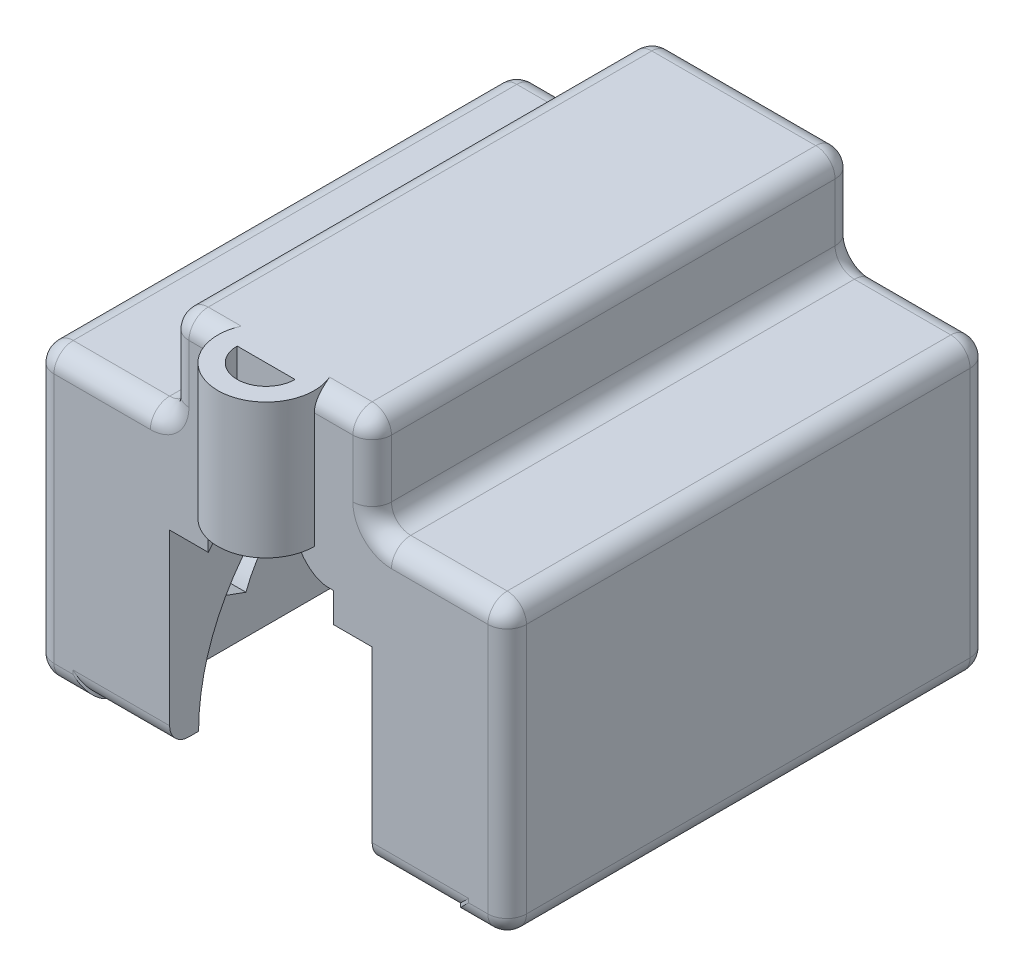
SolidWorks part; units mm, degrees
ref_plane "Front Plane" through (0, 0, 0) normal (0, 0, 1) x (1, 0, 0)
ref_plane "Top Plane" through (0, 0, 0) normal (0, 1, 0) x (1, 0, 0)
ref_plane "Right Plane" through (0, 0, 0) normal (1, 0, 0) x (0, 0, -1)
sketch "Sketch2" plane through (0, 0, 0) normal (0, 0, 1) x (1, 0, 0)
  line L0 (0, 0) -> (0, 38.1)
  line L1 (0, 38.1) -> (17.78, 38.1)
  line L2 (17.78, 38.1) -> (17.78, 50.8)
  line L3 (17.78, 50.8) -> (44.45, 50.8)
  line L4 (44.45, 50.8) -> (44.45, 38.1)
  line L5 (44.45, 38.1) -> (62.23, 38.1)
  line L6 (62.23, 38.1) -> (62.23, 0)
  line L8 (54.61, 0) -> (62.23, 0)
  line L9 (54.61, 0) -> (54.61, 0.508)
  line L10 (54.61, 0.508) -> (7.62, 0.508)
  line L11 (7.62, 0.508) -> (7.62, 0)
  line L12 (7.62, 0) -> (0, 0)
  dimension "D1" = 38.1
  dimension "D2" = 12.7
  dimension "D3" = 12.7
  dimension "D4" = 17.78
  dimension "D5" = 17.78
  dimension "D6" = 7.62
  dimension "D7" = 7.62
  dimension "D8" = 46.99
  dimension "D9" = 0.508
  dimension "D10" = 38.1
extrude "Boss-Extrude1" add sketch "Sketch2" along normal blind 58.42
sketch "Sketch3" plane through (0, 0.508, 0) normal (0, -1, 0) x (1, 0, 0)
  line L0 (7.62, 58.42) -> (54.61, 58.42) construction
  line L1 (7.62, 0) -> (54.61, 0) construction
  line L2 (7.62, 58.42) -> (7.62, 0) construction
  line L3 (54.61, 58.42) -> (54.61, 0) construction
  line L12 (10.16, 3.81) -> (52.07, 3.81)
  line L13 (52.07, 3.81) -> (52.07, 54.61)
  line L14 (52.07, 54.61) -> (10.16, 54.61)
  line L15 (10.16, 54.61) -> (10.16, 3.81)
  dimension "D1" = 3.81
  dimension "D2" = 3.81
  dimension "D3" = 2.54
  dimension "D4" = 2.54
extrude "Cut-Extrude1" cut sketch "Sketch3" against normal blind 2.54
sketch "Sketch15" plane through (0, 0.508, 0) normal (0, -1, 0) x (-1, 0, 0)
  line L0 (-52.07, -29.21) -> (-10.16, -29.21) construction
  line L1 (-52.07, -3.81) -> (-52.07, -54.61) construction
  line L2 (-10.16, -54.61) -> (-10.16, -3.81) construction
  line L3 (-52.07, -29.21) -> (-52.07, -54.61)
  line L4 (-52.07, -54.61) -> (-10.16, -54.61)
  line L6 (-10.16, -54.61) -> (-10.16, -29.21)
  line L7 (-10.16, -3.81) -> (-52.07, -3.81) construction
  line L8 (-52.07, -54.61) -> (-10.16, -54.61) construction
  line L9 (-52.07, -29.21) -> (-10.16, -29.21)
  dimension "D1" = 0
revolve "Cut-Revolve2" cut sketch "Sketch15" angle 360 about L0
sketch "Sketch17" plane through (0, 0.508, 0) normal (0, -1, 0) x (1, 0, 0)
  line L0 (52.07, 3.81) -> (52.07, 54.61) construction
  line L1 (46.99, 1.27) -> (15.24, 1.27)
  line L2 (46.99, 1.27) -> (46.99, 29.21)
  line L3 (46.99, 29.21) -> (15.24, 29.21)
  line L4 (15.24, 1.27) -> (15.24, 29.21)
  line L5 (7.62, 58.42) -> (7.62, 0) construction
  line L6 (54.61, 58.42) -> (54.61, 0) construction
  line L7 (7.62, 0) -> (54.61, 0) construction
  point P12 (52.07, 29.21)
  dimension "D1" = 0
  dimension "D2" = 7.62
  dimension "D3" = 7.62
  dimension "D4" = 1.27
revolve "Cut-Revolve3" cut sketch "Sketch17" angle 230 about L3 other way angle 20
sketch "Sketch18" plane through (0, 0.508, 0) normal (0, -1, 0) x (1, 0, 0)
  line L0 (10.16, 3.81) -> (15.24, 3.81) construction
  line L1 (52.07, 29.21) -> (46.99, 29.21)
  line L2 (52.07, 29.21) -> (52.07, 47.752)
  line L3 (52.07, 47.752) -> (46.99, 47.752)
  line L4 (46.99, 29.21) -> (46.99, 47.752)
  line L5 (10.16, 47.752) -> (15.24, 47.752)
  line L6 (10.16, 47.752) -> (10.16, 29.21)
  line L7 (10.16, 29.21) -> (15.24, 29.21)
  line L8 (15.24, 47.752) -> (15.24, 29.21)
  line L33 (52.07, 3.81) -> (52.07, 54.61) construction
  line L34 (10.16, 29.21) -> (52.07, 29.21) construction
  line L35 (10.16, 54.61) -> (52.07, 54.61) construction
  line L36 (15.24, 57.15) -> (15.24, 54.61) construction
  line L38 (46.99, 54.61) -> (46.99, 57.15) construction
  line L41 (10.16, 47.752) -> (7.62, 47.752)
  line L42 (10.16, 47.752) -> (10.16, 44.196)
  line L43 (10.16, 44.196) -> (7.62, 44.196)
  line L44 (7.62, 47.752) -> (7.62, 44.196)
  line L45 (10.16, 54.61) -> (15.24, 54.61) construction
  line L46 (52.07, 47.752) -> (54.61, 47.752)
  line L47 (52.07, 47.752) -> (52.07, 44.196)
  line L48 (52.07, 44.196) -> (54.61, 44.196)
  line L49 (54.61, 47.752) -> (54.61, 44.196)
  line L51 (10.16, 54.61) -> (10.16, 3.81) construction
  point P34 (12.7, 3.81)
  dimension "D1" = 25.4
  dimension "D2" = 6.858
  dimension "D3" = 3.556
  dimension "D4" = 6.858
  dimension "D5" = 2.54
  dimension "D6" = 0
  dimension "D7" = 3.556
  dimension "D8" = 2.54
sketch "Sketch19" plane through (0, 0, 0) normal (0, 0, -1) x (-1, 0, 0)
  line L24 (-7.62, 0) -> (0, 0)
  line L25 (0, 0) -> (0, 38.1)
  line L26 (0, 38.1) -> (-17.78, 38.1)
  line L27 (-17.78, 38.1) -> (-17.78, 50.8)
  line L28 (-17.78, 50.8) -> (-44.45, 50.8)
  line L29 (-44.45, 50.8) -> (-44.45, 38.1)
  line L30 (-44.45, 38.1) -> (-62.23, 38.1)
  line L31 (-62.23, 38.1) -> (-62.23, 0)
  line L32 (-62.23, 0) -> (-54.61, 0)
  line L33 (-54.61, 0) -> (-54.61, 0.508)
  line L34 (-54.61, 0.508) -> (-7.62, 0.508)
  line L35 (-7.62, 0.508) -> (-7.62, 0)
  line L36 (-7.62, 0) -> (0, 0)
  line L37 (0, 0) -> (0, 38.1)
  line L38 (0, 38.1) -> (-17.78, 38.1)
  line L39 (-17.78, 38.1) -> (-17.78, 50.8)
  line L40 (-17.78, 50.8) -> (-44.45, 50.8)
  line L41 (-44.45, 50.8) -> (-44.45, 38.1)
  line L42 (-44.45, 38.1) -> (-62.23, 38.1)
  line L43 (-62.23, 38.1) -> (-62.23, 0)
  line L44 (-62.23, 0) -> (-54.61, 0)
  line L45 (-54.61, 0) -> (-54.61, 0.508)
  line L46 (-54.61, 0.508) -> (-7.62, 0.508)
  line L47 (-7.62, 0.508) -> (-7.62, 0)
  dimension "D1" = 0
extrude "Boss-Extrude2" add sketch "Sketch19" along normal blind 2.54
sketch "Sketch20" plane through (0, 0, 58.42) normal (0, 0, 1) x (1, 0, 0)
  line L24 (0, 0) -> (7.62, 0)
  line L25 (7.62, 0) -> (7.62, 0.508)
  line L26 (7.62, 0.508) -> (54.61, 0.508)
  line L27 (54.61, 0.508) -> (54.61, 0)
  line L28 (54.61, 0) -> (62.23, 0)
  line L29 (62.23, 0) -> (62.23, 38.1)
  line L30 (62.23, 38.1) -> (44.45, 38.1)
  line L31 (44.45, 38.1) -> (44.45, 50.8)
  line L32 (44.45, 50.8) -> (17.78, 50.8)
  line L33 (17.78, 50.8) -> (17.78, 38.1)
  line L34 (17.78, 38.1) -> (0, 38.1)
  line L35 (0, 38.1) -> (0, 0)
  line L36 (0, 0) -> (7.62, 0)
  line L37 (7.62, 0) -> (7.62, 0.508)
  line L38 (7.62, 0.508) -> (54.61, 0.508)
  line L39 (54.61, 0.508) -> (54.61, 0)
  line L40 (54.61, 0) -> (62.23, 0)
  line L41 (62.23, 0) -> (62.23, 38.1)
  line L42 (62.23, 38.1) -> (44.45, 38.1)
  line L43 (44.45, 38.1) -> (44.45, 50.8)
  line L44 (44.45, 50.8) -> (17.78, 50.8)
  line L45 (17.78, 50.8) -> (17.78, 38.1)
  line L46 (17.78, 38.1) -> (0, 38.1)
  line L47 (0, 38.1) -> (0, 0)
  dimension "D1" = 0
extrude "Boss-Extrude3" add sketch "Sketch20" along normal blind 2.54
revolve "Cut-Revolve4" cut sketch "Sketch18" angle 340 about L34 region at (49.53, 0.508, 38.481) region at (12.7, 0.508, 38.481) region at (8.89, 0.508, 45.974)
fillet "Fillet2" radius 2.54 32 edges at (62.23, 0, 29.21) (62.23, 38.1, 29.21) (44.45, 38.1, 29.21) (0, 0, 29.21) (0, 38.1, 29.21) (17.78, 38.1, 29.21) (44.45, 50.8, 29.21) (17.78, 50.8, 29.21) (53.34, 38.1, 60.96) (53.34, 38.1, -2.54) (62.23, 19.05, 60.96) (62.23, 19.05, -2.54) (44.45, 44.45, 60.96) (44.45, 44.45, -2.54) (0, 19.05, 60.96) (0, 19.05, -2.54) (8.89, 38.1, 60.96) (8.89, 38.1, -2.54) (17.78, 44.45, 60.96) (17.78, 44.45, -2.54) (31.115, 50.8, 60.96) (31.115, 50.8, -2.54) (58.42, 0, -2.54) (54.61, 0.254, -2.54) (31.115, 0.508, -2.54) (7.62, 0.254, -2.54) (3.81, 0, -2.54) (54.61, 0.254, 60.96) (3.81, 0, 60.96) (7.62, 0.254, 60.96) (31.115, 0.508, 60.96) (58.42, 0, 60.96)
sketch "Sketch21" plane through (0, 0, 0) normal (0, -1, 0) x (1, 0, 0)
  line L0 (59.69, 29.21) -> (2.54, 29.21) construction
  line L1 (59.69, 0) -> (59.69, 58.42) construction
  line L2 (2.54, 58.42) -> (2.54, 0) construction
  line L3 (7.62, 58.42) -> (7.62, 14.224) construction
  line L4 (44.45, 29.21) -> (39.37, 29.21)
  line L5 (44.45, 29.21) -> (44.45, 69.85)
  line L6 (44.45, 69.85) -> (39.37, 69.85)
  line L7 (39.37, 29.21) -> (39.37, 54.61)
  line L8 (17.78, 29.21) -> (22.86, 29.21)
  line L9 (17.78, 29.21) -> (17.78, 69.85)
  line L10 (17.78, 69.85) -> (22.86, 69.85)
  line L11 (22.86, 29.21) -> (22.86, 54.61)
  line L12 (54.61, 58.42) -> (54.61, 14.224) construction
  line L13 (28.575, 72.39) -> (22.86, 72.39)
  line L14 (39.37, 54.61) -> (22.86, 54.61)
  line L15 (39.37, 69.85) -> (39.37, 72.39)
  line L16 (39.37, 72.39) -> (33.655, 72.39)
  line L17 (22.86, 69.85) -> (22.86, 72.39)
  line L19 (28.575, 72.39) -> (28.575, 77.47)
  line L20 (28.575, 77.47) -> (33.655, 77.47)
  line L21 (33.655, 72.39) -> (33.655, 77.47)
  dimension "D1" = 10.16
  dimension "D2" = 5.08
  dimension "D3" = 10.16
  dimension "D4" = 5.08
  dimension "D5" = 40.64
  dimension "D6" = 40.64
  dimension "D7" = 15.24
  dimension "D8" = 2.54
  dimension "D9" = 16.51
  dimension "D10" = 5.08
  dimension "D11" = 5.08
  dimension "D12" = 5.715
  dimension "D13" = 5.08
revolve "Cut-Revolve5" cut sketch "Sketch21" angle 51 about L0
fillet "Fillet3" radius 7.62 1 edges at (31.115, 20.0448, 45.4419)
sketch "Sketch23" plane through (0, 50.8, 0) normal (0, 1, 0) x (1, 0, 0)
  line L1 (41.91, -60.96) -> (20.32, -60.96) construction
  line L2 (41.91, -58.42) -> (41.91, 0) construction
  circle A0 centre (30.48, -60.96) radius 6.35
  point P4 (0, 0)
  dimension "D1" = 12.7
  dimension "D2" = 11.43
extrude "Boss-Extrude4" add sketch "Sketch23" against normal blind 17.78
sketch "Sketch24" plane through (0, 50.8, 0) normal (0, 1, 0) x (1, 0, 0)
  line L0 (26.67, -60.96) -> (34.29, -60.96)
  line L1 (36.2999, -58.42) -> (41.91, -58.42) construction
  arc A0 (34.29, -60.96) -> (26.67, -60.96) centre (30.48, -60.96) cw
  arc A2 (24.6601, -58.42) -> (36.2999, -58.42) centre (30.48, -60.96) ccw construction
  point P3 (0, 0)
  dimension "D1" = 2.54
extrude "Cut-Extrude2" cut sketch "Sketch24" against normal blind 17.78
fillet "Fillet4" radius 7.62 1 edges at (31.115, 33.02, 60.96)
fillet "Fillet5" radius 5.08 2 edges at (28.575, 31.3685, 58.8838) (33.655, 31.3685, 58.8838)
